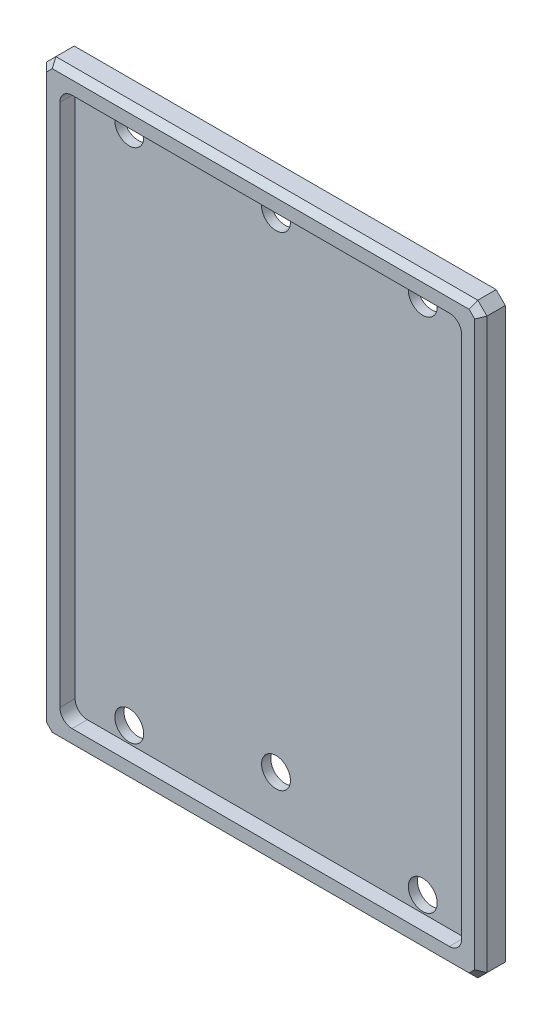
SolidWorks part; units mm, degrees
material "AISI 304"
ref_plane "Front Plane" through (0, 0, 0) normal (0, 0, 1) x (1, 0, 0)
ref_plane "Top Plane" through (0, 0, 0) normal (0, 1, 0) x (1, 0, 0)
ref_plane "Right Plane" through (0, 0, 0) normal (1, 0, 0) x (0, 0, -1)
sketch "Sketch1" plane through (0, 0, 0) normal (0, 0, 1) x (1, 0, 0)
  line L1 (114.3, -152.4) -> (-114.3, -152.4)
  line L2 (114.3, -152.4) -> (114.3, 152.4)
  line L3 (114.3, 152.4) -> (-114.3, 152.4)
  line L4 (-114.3, -152.4) -> (-114.3, 152.4)
  line L5 (114.3, -152.4) -> (-114.3, 152.4) construction
  line L6 (114.3, 152.4) -> (-114.3, -152.4) construction
  point P0 (0, 0)
  dimension "D1" = 228.6
  dimension "D2" = 304.8
extrude "Boss-Extrude1" add sketch "Sketch1" along normal blind 12.7
sketch "Sketch2" plane through (0, 0, 12.7) normal (0, 0, 1) x (1, 0, 0)
  line L0 (-114.3, 152.4) -> (-114.3, -152.4) construction
  line L1 (97.95, -142.4) -> (-97.95, -142.4)
  line L2 (104.3, -136.05) -> (104.3, 136.05)
  line L3 (97.95, 142.4) -> (-97.95, 142.4)
  line L4 (-104.3, -136.05) -> (-104.3, 136.05)
  line L5 (104.3, -142.4) -> (-104.3, 142.4) construction
  line L6 (104.3, 142.4) -> (-104.3, -142.4) construction
  line L7 (114.3, 152.4) -> (-114.3, 152.4) construction
  arc A0 (-97.95, -142.4) -> (-104.3, -136.05) centre (-97.95, -136.05) cw
  arc A1 (97.95, -142.4) -> (104.3, -136.05) centre (97.95, -136.05) ccw
  arc A2 (104.3, 136.05) -> (97.95, 142.4) centre (97.95, 136.05) ccw
  arc A3 (-97.95, 142.4) -> (-104.3, 136.05) centre (-97.95, 136.05) ccw
  point P0 (0, 0)
  dimension "D3" = 6.35
  dimension "D1" = 10
  dimension "D2" = 10
extrude "Cut-Extrude1" cut sketch "Sketch2" against normal blind 7.9375
sketch "Sketch4" plane through (0, 0, 4.7625) normal (0, 0, 1) x (1, 0, 0)
  line L0 (-97.95, -142.4) -> (97.95, -142.4) construction
  line L1 (97.95, 142.4) -> (-97.95, 142.4) construction
  line L4 (-114.3, 152.4) -> (-114.3, -152.4) construction
  line L5 (114.3, -152.4) -> (114.3, 152.4) construction
  line L8 (-97.95, -142.4) -> (97.95, -142.4) construction
  circle A0 centre (-76.2, 134.05) radius 7.5
  circle A1 centre (76.2, 134.05) radius 7.5
  circle A2 centre (-76.2, -134.05) radius 7.5
  circle A3 centre (76.2, -134.05) radius 7.5
  circle A4 centre (0, 134.05) radius 7.5
  circle A5 centre (0, -117) radius 7.5
  dimension "D1" = 15
  dimension "D2" = 15
  dimension "D3" = 15
  dimension "D4" = 15
  dimension "D13" = 15
  dimension "D14" = 15
  dimension "D15" = 8.35
  dimension "D5" = 0
  dimension "D6" = 38.1
  dimension "D7" = 38.1
  dimension "D8" = 0
  dimension "D9" = 8.35
  dimension "D10" = 38.1
  dimension "D11" = 38.1
  dimension "D16" = 25.4
extrude "Cut-Extrude2" cut sketch "Sketch4" against normal through all
hole_wizard "M4x0.7 Tapped Hole1" positions "Sketch8" profile "Sketch9" tap size "M4x0.7" standard "ANSI Metric"
sketch "Sketch8" plane through (0, 0, 0) normal (0, 0, -1) x (-1, 0, 0)
  line L0 (114.3, -152.4) -> (-114.3, -152.4) construction
  line L1 (-114.3, -152.4) -> (-114.3, 152.4) construction
  point P0 (-109.3, -102.4)
  point P2 (-109.3, 0)
  point P4 (-109.3, 113.6)
  point P14 (-114.3, 0)
  dimension "D1" = 266
  dimension "D2" = 5
  dimension "D3" = 50
sketch "Sketch9" plane through (109.3, -102.4, 0) normal (1, 0, 0) x (0, 1, 0)
  line L0 (0, 0) -> (0, 6.3914)
  line L1 (0, 6.3914) -> (1.65, 5.4)
  line L2 (1.65, 5.4) -> (1.65, 0)
  line L5 (1.65, 0) -> (0, 0)
  line L10 (0, 6.3914) -> (-1.65, 5.4) construction
  line L11 (0, -6.35) -> (0, 107.95) construction
  dimension "Tap Drill Dia." = 3.3
  dimension "Tap Drill Depth" = 5.4
  dimension "Drill Angle" = 118
cosmetic thread "Hole Thread1" parameters "D1"=3, "D2"=4.3
cosmetic thread "Hole Thread2" parameters "D1"=3, "D2"=4.3
cosmetic thread "Hole Thread3" parameters "D1"=3, "D2"=4.3
chamfer "Chamfer1" distance 4.7625 angle 45 4 edges at (-114.3, -152.4, 6.35) (114.3, -152.4, 6.35) (-114.3, 152.4, 6.35) (114.3, 152.4, 6.35)
chamfer "Chamfer2" distance 3.175 angle 45 8 edges at (-111.9188, 150.0187, 12.7) (0, 152.4, 12.7) (111.9187, 150.0187, 12.7) (114.3, 0, 12.7) (111.9187, -150.0188, 12.7) (0, -152.4, 12.7) (-111.9188, -150.0188, 12.7) (-114.3, 0, 12.7)
